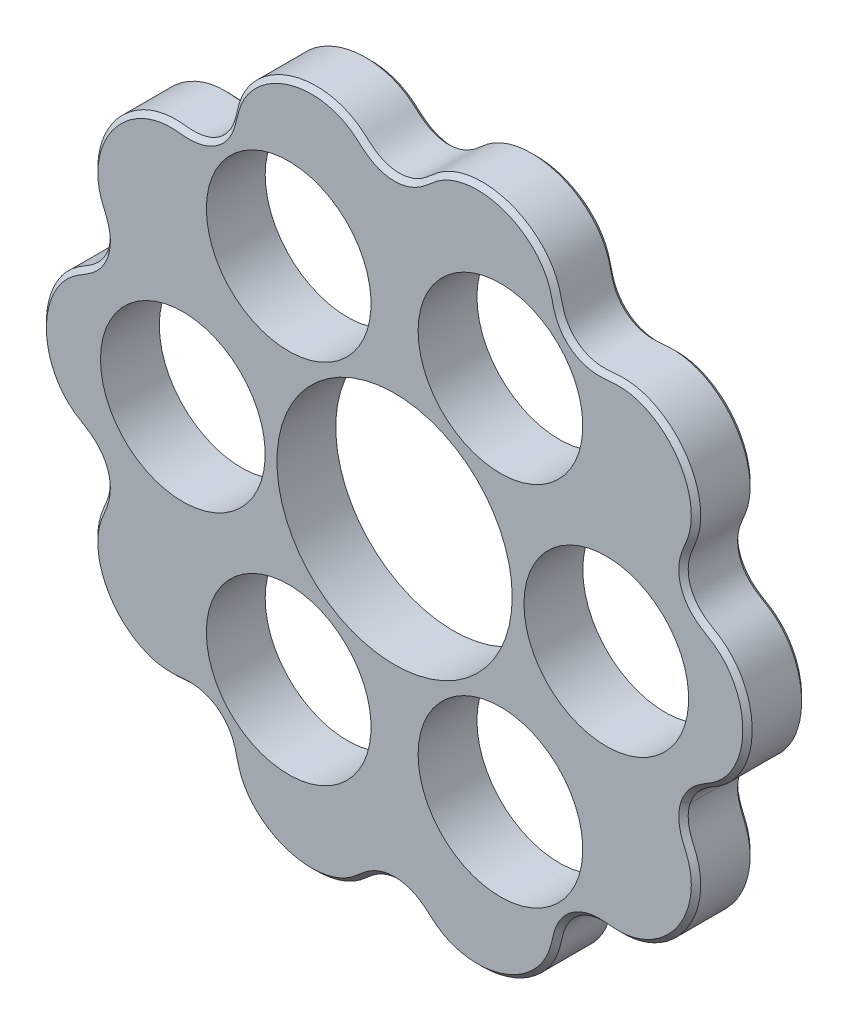
SolidWorks part; units mm, degrees
ref_plane "Front Plane" through (0, 0, 0) normal (0, 0, 1) x (1, 0, 0)
ref_plane "Top Plane" through (0, 0, 0) normal (0, 1, 0) x (1, 0, 0)
ref_plane "Right Plane" through (0, 0, 0) normal (1, 0, 0) x (0, 0, -1)
ref_plane "Plane1" through (0, 0, 2.5) normal (0, 0, -1) x (-1, 0, 0)
sketch "Sketch1" plane through (0, 0, 2.5) normal (0, 0, -1) x (-1, 0, 0)
  spline S0 degree 5 poles (13.3637, 4.0172) (13.3679, 4.0044) (13.3764, 3.979) (13.39, 3.941) (13.4096, 3.891) (13.4366, 3.8295) (13.466, 3.7691) (13.4977, 3.7099) (13.5318, 3.652) (13.5681, 3.5955) (13.6065, 3.5404) (13.647, 3.4868) (13.6895, 3.4348) (13.7339, 3.3844) (13.7801, 3.3357) (13.828, 3.2886) (13.8775, 3.2433) (13.9285, 3.1996) (13.9809, 3.1576) (14.0345, 3.1172) (14.0892, 3.0782) (14.1448, 3.0407) (14.2012, 3.0043) (14.2582, 2.9689) (14.3156, 2.934) (14.3731, 2.8995) (14.4306, 2.8649) (14.4879, 2.83) (14.5447, 2.7944) (14.601, 2.7578) (14.6567, 2.7203) (14.7115, 2.6816) (14.7655, 2.6417) (14.8185, 2.6005) (14.8705, 2.5581) (14.9216, 2.5145) (14.9715, 2.4697) (15.0204, 2.4237) (15.0682, 2.3765) (15.1148, 2.3283) (15.1604, 2.279) (15.2048, 2.2286) (15.248, 2.1773) (15.2901, 2.125) (15.3309, 2.0718) (15.3707, 2.0177) (15.4092, 1.9627) (15.4465, 1.9069) (15.4827, 1.8504) (15.5176, 1.7931) (15.5513, 1.735) (15.5839, 1.6763) (15.6152, 1.617) (15.6453, 1.557) (15.6742, 1.4964) (15.7019, 1.4353) (15.7283, 1.3736) (15.7536, 1.3114) (15.7776, 1.2487) (15.8004, 1.1856) (15.822, 1.1221) (15.8423, 1.0581) (15.8614, 0.9938) (15.8793, 0.9291) (15.896, 0.8641) (15.9114, 0.7988) (15.9256, 0.7332) (15.9386, 0.6673) (15.9503, 0.6012) (15.9608, 0.535) (15.97, 0.4685) (15.9781, 0.4019) (15.9849, 0.3351) (15.9904, 0.2682) (15.9947, 0.2012) (15.9978, 0.1342) (15.9997, 0.0671) (16.0003, 0) (15.9997, -0.0671) (15.9978, -0.1342) (15.9947, -0.2012) (15.9904, -0.2682) (15.9849, -0.3351) (15.9781, -0.4019) (15.97, -0.4685) (15.9608, -0.535) (15.9503, -0.6012) (15.9386, -0.6673) (15.9256, -0.7332) (15.9114, -0.7988) (15.896, -0.8641) (15.8793, -0.9291) (15.8614, -0.9938) (15.8423, -1.0581) (15.822, -1.1221) (15.8004, -1.1856) (15.7776, -1.2487) (15.7536, -1.3114) (15.7283, -1.3736) (15.7019, -1.4353) (15.6742, -1.4964) (15.6453, -1.557) (15.6152, -1.617) (15.5839, -1.6763) (15.5513, -1.735) (15.5176, -1.7931) (15.4827, -1.8504) (15.4465, -1.9069) (15.4092, -1.9627) (15.3707, -2.0177) (15.3309, -2.0718) (15.2901, -2.125) (15.248, -2.1773) (15.2048, -2.2286) (15.1604, -2.279) (15.1148, -2.3283) (15.0682, -2.3765) (15.0204, -2.4237) (14.9715, -2.4697) (14.9216, -2.5145) (14.8705, -2.5581) (14.8185, -2.6005) (14.7655, -2.6417) (14.7115, -2.6816) (14.6567, -2.7203) (14.601, -2.7578) (14.5447, -2.7944) (14.4879, -2.83) (14.4306, -2.8649) (14.3731, -2.8995) (14.3156, -2.934) (14.2582, -2.9689) (14.2012, -3.0043) (14.1448, -3.0407) (14.0892, -3.0782) (14.0345, -3.1172) (13.9809, -3.1576) (13.9285, -3.1996) (13.8775, -3.2433) (13.828, -3.2886) (13.7801, -3.3357) (13.7339, -3.3844) (13.6895, -3.4348) (13.647, -3.4868) (13.6065, -3.5404) (13.5681, -3.5955) (13.5318, -3.652) (13.4977, -3.7099) (13.466, -3.7691) (13.4366, -3.8295) (13.4096, -3.891) (13.3851, -3.9536) (13.3631, -4.017) (13.3436, -4.0813) (13.3267, -4.1463) (13.3124, -4.2119) (13.3006, -4.2781) (13.2915, -4.3446) (13.285, -4.4115) (13.2811, -4.4785) (13.2798, -4.5457) (13.2811, -4.6128) (13.2849, -4.6799) (13.2912, -4.7468) (13.3, -4.8133) (13.3111, -4.8796) (13.3245, -4.9454) (13.3401, -5.0107) (13.3578, -5.0754) (13.3774, -5.1397) (13.3987, -5.2033) (13.4217, -5.2664) (13.4459, -5.329) (13.4712, -5.3911) (13.4971, -5.453) (13.5234, -5.5147) (13.5496, -5.5765) (13.5753, -5.6385) (13.6004, -5.7007) (13.6245, -5.7633) (13.6474, -5.8264) (13.669, -5.89) (13.6892, -5.954) (13.7079, -6.0184) (13.7251, -6.0833) (13.7408, -6.1486) (13.7548, -6.2142) (13.7673, -6.2802) (13.7783, -6.3464) (13.7877, -6.4129) (13.7955, -6.4795) (13.8018, -6.5463) (13.8066, -6.6133) (13.8099, -6.6803) (13.8117, -6.7474) (13.8121, -6.8145) (13.8109, -6.8817) (13.8083, -6.9487) (13.8043, -7.0157) (13.7989, -7.0826) (13.7921, -7.1494) (13.7839, -7.216) (13.7744, -7.2824) (13.7635, -7.3487) (13.7513, -7.4147) (13.7377, -7.4804) (13.7229, -7.5458) (13.7067, -7.611) (13.6893, -7.6758) (13.6707, -7.7403) (13.6508, -7.8044) (13.6296, -7.8681) (13.6073, -7.9313) (13.5837, -7.9942) (13.559, -8.0566) (13.5331, -8.1185) (13.506, -8.1799) (13.4778, -8.2408) (13.4484, -8.3011) (13.418, -8.3609) (13.3864, -8.4202) (13.3537, -8.4788) (13.32, -8.5368) (13.2852, -8.5942) (13.2493, -8.6509) (13.2124, -8.7069) (13.1745, -8.7623) (13.1355, -8.817) (13.0956, -8.8709) (13.0546, -8.9241) (13.0127, -8.9765) (12.9699, -9.0281) (12.926, -9.079) (12.8813, -9.129) (12.8356, -9.1782) (12.7891, -9.2265) (12.7416, -9.274) (12.6933, -9.3205) (12.6441, -9.3662) (12.5941, -9.4109) (12.5432, -9.4547) (12.4915, -9.4975) (12.439, -9.5393) (12.3857, -9.5801) (12.3317, -9.6199) (12.2769, -9.6586) (12.2213, -9.6963) (12.1651, -9.7329) (12.1081, -9.7684) (12.0504, -9.8027) (11.9921, -9.8359) (11.9331, -9.8679) (11.8735, -9.8988) (11.8133, -9.9284) (11.7525, -9.9567) (11.6911, -9.9838) (11.6291, -10.0097) (11.5666, -10.0342) (11.5036, -10.0574) (11.4402, -10.0792) (11.3762, -10.0996) (11.3119, -10.1186) (11.2471, -10.1362) (11.1819, -10.1523) (11.1164, -10.167) (11.0506, -10.1801) (10.9845, -10.1917) (10.9181, -10.2018) (10.8515, -10.2103) (10.7848, -10.2172) (10.7179, -10.2225) (10.6508, -10.2262) (10.5838, -10.2283) (10.5166, -10.2289) (10.4495, -10.2279) (10.3825, -10.2256) (10.3154, -10.2221) (10.2485, -10.2175) (10.1816, -10.2121) (10.1148, -10.2063) (10.0479, -10.2004) (9.9811, -10.1948) (9.9141, -10.19) (9.8471, -10.1863) (9.7801, -10.184) (9.7129, -10.1833) (9.6458, -10.1845) (9.5787, -10.1877) (9.5118, -10.1931) (9.4451, -10.2007) (9.3787, -10.2106) (9.3126, -10.2228) (9.2471, -10.2375) (9.1821, -10.2546) (9.1179, -10.2741) (9.0544, -10.2961) (8.9918, -10.3205) (8.9303, -10.3474) (8.8698, -10.3766) (8.8105, -10.4082) (8.7525, -10.4421) (8.6959, -10.4783) (8.6408, -10.5167) (8.5873, -10.5572) (8.5354, -10.5999) (8.4852, -10.6445) (8.4368, -10.6912) (8.3903, -10.7396) (8.3458, -10.7899) (8.3032, -10.8419) (8.2627, -10.8954) (8.2243, -10.9505) (8.1879, -11.007) (8.1537, -11.0648) (8.1217, -11.1238) (8.0917, -11.1839) (8.0639, -11.245) (8.0381, -11.307) (8.0144, -11.3698) (7.9925, -11.4333) (7.9724, -11.4974) (7.9538, -11.5619) (7.9367, -11.6267) (7.9206, -11.6919) (7.9052, -11.7572) (7.8901, -11.8226) (7.875, -11.8879) (7.8595, -11.9532) (7.8431, -12.0183) (7.8258, -12.0831) (7.8073, -12.1476) (7.7874, -12.2118) (7.7661, -12.2754) (7.7434, -12.3386) (7.7192, -12.4012) (7.6934, -12.4632) (7.6663, -12.5245) (7.6376, -12.5852) (7.6075, -12.6452) (7.5761, -12.7045) (7.5432, -12.7631) (7.5091, -12.8208) (7.4736, -12.8778) (7.4369, -12.934) (7.3989, -12.9893) (7.3597, -13.0438) (7.3193, -13.0974) (7.2778, -13.1502) (7.2352, -13.202) (7.1915, -13.253) (7.1467, -13.303) (7.101, -13.3521) (7.0542, -13.4002) (7.0064, -13.4474) (6.9578, -13.4936) (6.9082, -13.5388) (6.8577, -13.583) (6.8063, -13.6262) (6.7542, -13.6685) (6.7012, -13.7096) (6.6474, -13.7498) (6.5928, -13.7889) (6.5376, -13.827) (6.4816, -13.864) (6.4249, -13.8999) (6.3675, -13.9347) (6.3095, -13.9685) (6.2509, -14.0012) (6.1917, -14.0328) (6.1319, -14.0632) (6.0716, -14.0926) (6.0107, -14.1208) (5.9493, -14.1479) (5.8874, -14.1739) (5.825, -14.1987) (5.7622, -14.2223) (5.699, -14.2448) (5.6354, -14.2661) (5.5713, -14.2863) (5.507, -14.3053) (5.4422, -14.323) (5.3772, -14.3396) (5.3119, -14.355) (5.2463, -14.3692) (5.1804, -14.3821) (5.1144, -14.3939) (5.0481, -14.4044) (4.9816, -14.4136) (4.915, -14.4216) (4.8482, -14.4284) (4.7813, -14.4339) (4.7143, -14.4382) (4.6473, -14.4411) (4.5802, -14.4428) (4.5131, -14.4433) (4.446, -14.4424) (4.3789, -14.4402) (4.3119, -14.4367) (4.2449, -14.432) (4.1781, -14.4258) (4.1114, -14.4184) (4.0449, -14.4097) (3.9785, -14.3996) (3.9124, -14.3881) (3.8465, -14.3753) (3.7809, -14.3611) (3.7156, -14.3456) (3.6506, -14.3287) (3.5861, -14.3105) (3.5219, -14.2908) (3.4581, -14.2697) (3.3949, -14.2473) (3.3321, -14.2235) (3.27, -14.1982) (3.2084, -14.1716) (3.1474, -14.1435) (3.0871, -14.114) (3.0275, -14.0831) (2.9686, -14.0509) (2.9105, -14.0172) (2.8533, -13.9822) (2.7969, -13.9458) (2.7414, -13.9081) (2.6867, -13.8691) (2.633, -13.8289) (2.5801, -13.7876) (2.528, -13.7453) (2.4765, -13.7022) (2.4256, -13.6586) (2.3749, -13.6146) (2.3243, -13.5705) (2.2735, -13.5267) (2.2221, -13.4835) (2.1701, -13.4411) (2.1172, -13.3998) (2.0633, -13.3598) (2.0083, -13.3213) (1.9521, -13.2845) (1.8948, -13.2495) (1.8364, -13.2164) (1.7769, -13.1854) (1.7162, -13.1565) (1.6546, -13.1298) (1.592, -13.1055) (1.5285, -13.0835) (1.4643, -13.064) (1.3993, -13.047) (1.3337, -13.0325) (1.2676, -13.0206) (1.2011, -13.0113) (1.1342, -13.0047) (1.0672, -13.0007) (1, -12.9993) (0.9328, -13.0007) (0.8658, -13.0047) (0.7989, -13.0113) (0.7324, -13.0206) (0.6663, -13.0325) (0.6007, -13.047) (0.5357, -13.064) (0.4715, -13.0835) (0.408, -13.1055) (0.3454, -13.1298) (0.2838, -13.1565) (0.2231, -13.1854) (0.1636, -13.2164) (0.1052, -13.2495) (0.0479, -13.2845) (-0.0083, -13.3213) (-0.0633, -13.3598) (-0.1172, -13.3998) (-0.1701, -13.4411) (-0.2221, -13.4835) (-0.2735, -13.5267) (-0.3243, -13.5705) (-0.3749, -13.6146) (-0.4256, -13.6586) (-0.4765, -13.7022) (-0.528, -13.7453) (-0.5801, -13.7876) (-0.633, -13.8289) (-0.6867, -13.8691) (-0.7414, -13.9081) (-0.7969, -13.9458) (-0.8533, -13.9822) (-0.9105, -14.0172) (-0.9686, -14.0509) (-1.0275, -14.0831) (-1.0871, -14.114) (-1.1474, -14.1435) (-1.2084, -14.1716) (-1.27, -14.1982) (-1.3321, -14.2235) (-1.3949, -14.2473) (-1.4581, -14.2697) (-1.5219, -14.2908) (-1.5861, -14.3105) (-1.6506, -14.3287) (-1.7156, -14.3456) (-1.7809, -14.3611) (-1.8465, -14.3753) (-1.9124, -14.3881) (-1.9785, -14.3996) (-2.0449, -14.4097) (-2.1114, -14.4184) (-2.1781, -14.4258) (-2.2449, -14.432) (-2.3119, -14.4367) (-2.3789, -14.4402) (-2.446, -14.4424) (-2.5131, -14.4433) (-2.5802, -14.4428) (-2.6473, -14.4411) (-2.7143, -14.4382) (-2.7813, -14.4339) (-2.8482, -14.4284) (-2.915, -14.4216) (-2.9816, -14.4136) (-3.0481, -14.4044) (-3.1144, -14.3939) (-3.1804, -14.3821) (-3.2463, -14.3692) (-3.3119, -14.355) (-3.3772, -14.3396) (-3.4422, -14.323) (-3.507, -14.3053) (-3.5713, -14.2863) (-3.6354, -14.2661) (-3.699, -14.2448) (-3.7622, -14.2223) (-3.825, -14.1987) (-3.8874, -14.1739) (-3.9493, -14.1479) (-4.0107, -14.1208) (-4.0716, -14.0926) (-4.1319, -14.0632) (-4.1917, -14.0328) (-4.2509, -14.0012) (-4.3095, -13.9685) (-4.3675, -13.9347) (-4.4249, -13.8999) (-4.4816, -13.864) (-4.5376, -13.827) (-4.5928, -13.7889) (-4.6474, -13.7498) (-4.7012, -13.7096) (-4.7542, -13.6685) (-4.8063, -13.6262) (-4.8577, -13.583) (-4.9082, -13.5388) (-4.9578, -13.4936) (-5.0064, -13.4474) (-5.0542, -13.4002) (-5.101, -13.3521) (-5.1467, -13.303) (-5.1915, -13.253) (-5.2352, -13.202) (-5.2778, -13.1502) (-5.3193, -13.0974) (-5.3597, -13.0438) (-5.3989, -12.9893) (-5.4369, -12.934) (-5.4736, -12.8778) (-5.5091, -12.8208) (-5.5432, -12.7631) (-5.5761, -12.7045) (-5.6075, -12.6452) (-5.6376, -12.5852) (-5.6663, -12.5245) (-5.6934, -12.4632) (-5.7192, -12.4012) (-5.7434, -12.3386) (-5.7661, -12.2754) (-5.7874, -12.2118) (-5.8073, -12.1476) (-5.8258, -12.0831) (-5.8431, -12.0183) (-5.8595, -11.9532) (-5.875, -11.8879) (-5.8901, -11.8226) (-5.9052, -11.7572) (-5.9206, -11.6919) (-5.9367, -11.6267) (-5.9538, -11.5619) (-5.9724, -11.4974) (-5.9925, -11.4333) (-6.0144, -11.3698) (-6.0381, -11.307) (-6.0639, -11.245) (-6.0917, -11.1839) (-6.1217, -11.1238) (-6.1537, -11.0648) (-6.1879, -11.007) (-6.2243, -10.9505) (-6.2627, -10.8954) (-6.3032, -10.8419) (-6.3458, -10.7899) (-6.3903, -10.7396) (-6.4368, -10.6912) (-6.4852, -10.6445) (-6.5354, -10.5999) (-6.5873, -10.5572) (-6.6408, -10.5167) (-6.6959, -10.4783) (-6.7525, -10.4421) (-6.8105, -10.4082) (-6.8698, -10.3766) (-6.9303, -10.3474) (-6.9918, -10.3205) (-7.0544, -10.2961) (-7.1179, -10.2741) (-7.1821, -10.2546) (-7.2471, -10.2375) (-7.3126, -10.2228) (-7.3787, -10.2106) (-7.4451, -10.2007) (-7.5118, -10.1931) (-7.5787, -10.1877) (-7.6458, -10.1845) (-7.7129, -10.1833) (-7.7801, -10.184) (-7.8471, -10.1863) (-7.9141, -10.19) (-7.9811, -10.1948) (-8.0479, -10.2004) (-8.1148, -10.2063) (-8.1816, -10.2121) (-8.2485, -10.2175) (-8.3154, -10.2221) (-8.3825, -10.2256) (-8.4495, -10.2279) (-8.5166, -10.2289) (-8.5838, -10.2283) (-8.6508, -10.2262) (-8.7179, -10.2225) (-8.7848, -10.2172) (-8.8515, -10.2103) (-8.9181, -10.2018) (-8.9845, -10.1917) (-9.0506, -10.1801) (-9.1164, -10.167) (-9.1819, -10.1523) (-9.2471, -10.1362) (-9.3119, -10.1186) (-9.3762, -10.0996) (-9.4402, -10.0792) (-9.5036, -10.0574) (-9.5666, -10.0342) (-9.6291, -10.0097) (-9.6911, -9.9838) (-9.7525, -9.9567) (-9.8133, -9.9284) (-9.8735, -9.8988) (-9.9331, -9.8679) (-9.9921, -9.8359) (-10.0504, -9.8027) (-10.1081, -9.7684) (-10.1651, -9.7329) (-10.2213, -9.6963) (-10.2769, -9.6586) (-10.3317, -9.6199) (-10.3857, -9.5801) (-10.439, -9.5393) (-10.4915, -9.4975) (-10.5432, -9.4547) (-10.5941, -9.4109) (-10.6441, -9.3662) (-10.6933, -9.3205) (-10.7416, -9.274) (-10.7891, -9.2265) (-10.8356, -9.1782) (-10.8813, -9.129) (-10.926, -9.079) (-10.9699, -9.0281) (-11.0127, -8.9765) (-11.0546, -8.9241) (-11.0956, -8.8709) (-11.1355, -8.817) (-11.1745, -8.7623) (-11.2124, -8.7069) (-11.2493, -8.6509) (-11.2852, -8.5942) (-11.32, -8.5368) (-11.3537, -8.4788) (-11.3864, -8.4202) (-11.418, -8.3609) (-11.4484, -8.3011) (-11.4778, -8.2408) (-11.506, -8.1799) (-11.5331, -8.1185) (-11.559, -8.0566) (-11.5837, -7.9942) (-11.6073, -7.9313) (-11.6296, -7.8681) (-11.6508, -7.8044) (-11.6707, -7.7403) (-11.6893, -7.6758) (-11.7067, -7.611) (-11.7229, -7.5458) (-11.7377, -7.4804) (-11.7513, -7.4147) (-11.7635, -7.3487) (-11.7744, -7.2824) (-11.7839, -7.216) (-11.7921, -7.1494) (-11.7989, -7.0826) (-11.8043, -7.0157) (-11.8083, -6.9487) (-11.8109, -6.8817) (-11.8121, -6.8145) (-11.8117, -6.7474) (-11.8099, -6.6803) (-11.8066, -6.6133) (-11.8018, -6.5463) (-11.7955, -6.4795) (-11.7877, -6.4129) (-11.7783, -6.3464) (-11.7673, -6.2802) (-11.7548, -6.2142) (-11.7408, -6.1486) (-11.7251, -6.0833) (-11.7079, -6.0184) (-11.6892, -5.954) (-11.669, -5.89) (-11.6474, -5.8264) (-11.6245, -5.7633) (-11.6004, -5.7007) (-11.5753, -5.6385) (-11.5496, -5.5765) (-11.5234, -5.5147) (-11.4971, -5.453) (-11.4712, -5.3911) (-11.4459, -5.329) (-11.4217, -5.2664) (-11.3987, -5.2033) (-11.3774, -5.1397) (-11.3578, -5.0754) (-11.3401, -5.0107) (-11.3245, -4.9454) (-11.3111, -4.8796) (-11.3, -4.8133) (-11.2912, -4.7468) (-11.2849, -4.6799) (-11.2811, -4.6128) (-11.2798, -4.5457) (-11.2811, -4.4785) (-11.285, -4.4115) (-11.2915, -4.3446) (-11.3006, -4.2781) (-11.3124, -4.2119) (-11.3267, -4.1463) (-11.3402, -4.0943) (-11.3515, -4.0556) (-11.3596, -4.03) (-11.3637, -4.0172) knots 50.343625 50.343625 50.343625 50.343625 50.343625 50.343625 50.41075 50.477875 50.545 50.612125 50.67925 50.746374 50.813499 50.880624 50.947749 51.014874 51.081999 51.149123 51.216248 51.283373 51.350498 51.417623 51.484748 51.551872 51.618997 51.686122 51.753247 51.820372 51.887497 51.954621 52.021746 52.088871 52.155996 52.223121 52.290246 52.35737 52.424495 52.49162 52.558745 52.62587 52.692995 52.760119 52.827244 52.894369 52.961494 53.028619 53.095744 53.162868 53.229993 53.297118 53.364243 53.431368 53.498493 53.565617 53.632742 53.699867 53.766992 53.834117 53.901242 53.968366 54.035491 54.102616 54.169741 54.236866 54.303991 54.371115 54.43824 54.505365 54.57249 54.639615 54.70674 54.773864 54.840989 54.908114 54.975239 55.042364 55.109489 55.176613 55.243738 55.310863 55.377988 55.445113 55.512238 55.579362 55.646487 55.713612 55.780737 55.847862 55.914987 55.982111 56.049236 56.116361 56.183486 56.250611 56.317736 56.38486 56.451985 56.51911 56.586235 56.65336 56.720485 56.787609 56.854734 56.921859 56.988984 57.056109 57.123234 57.190358 57.257483 57.324608 57.391733 57.458858 57.525983 57.593107 57.660232 57.727357 57.794482 57.861607 57.928732 57.995856 58.062981 58.130106 58.197231 58.264356 58.331481 58.398605 58.46573 58.532855 58.59998 58.667105 58.73423 58.801354 58.868479 58.935604 59.002729 59.069854 59.136979 59.204103 59.271228 59.338353 59.405478 59.472603 59.539728 59.606852 59.673977 59.741102 59.808227 59.875352 59.942477 60.009601 60.076726 60.143851 60.210976 60.278101 60.345226 60.41235 60.479475 60.5466 60.613725 60.68085 60.747975 60.815099 60.882224 60.949349 61.016474 61.083599 61.150724 61.217848 61.284973 61.352098 61.419223 61.486348 61.553473 61.620597 61.687722 61.754847 61.821972 61.889097 61.956222 62.023346 62.090471 62.157596 62.224721 62.291846 62.358971 62.426095 62.49322 62.560345 62.62747 62.694595 62.76172 62.828844 62.895969 62.963094 63.030219 63.097344 63.164469 63.231593 63.298718 63.365843 63.432968 63.500093 63.567218 63.634342 63.701467 63.768592 63.835717 63.902842 63.969967 64.037091 64.104216 64.171341 64.238466 64.305591 64.372716 64.43984 64.506965 64.57409 64.641215 64.70834 64.775465 64.842589 64.909714 64.976839 65.043964 65.111089 65.178214 65.245338 65.312463 65.379588 65.446713 65.513838 65.580963 65.648087 65.715212 65.782337 65.849462 65.916587 65.983712 66.050836 66.117961 66.185086 66.252211 66.319336 66.386461 66.453585 66.52071 66.587835 66.65496 66.722085 66.78921 66.856334 66.923459 66.990584 67.057709 67.124834 67.191959 67.259083 67.326208 67.393333 67.460458 67.527583 67.594708 67.661832 67.728957 67.796082 67.863207 67.930332 67.997457 68.064582 68.131706 68.198831 68.265956 68.333081 68.400206 68.467331 68.534455 68.60158 68.668705 68.73583 68.802955 68.87008 68.937204 69.004329 69.071454 69.138579 69.205704 69.272829 69.339953 69.407078 69.474203 69.541328 69.608453 69.675578 69.742702 69.809827 69.876952 69.944077 70.011202 70.078327 70.145451 70.212576 70.279701 70.346826 70.413951 70.481076 70.5482 70.615325 70.68245 70.749575 70.8167 70.883825 70.950949 71.018074 71.085199 71.152324 71.219449 71.286574 71.353698 71.420823 71.487948 71.555073 71.622198 71.689323 71.756447 71.823572 71.890697 71.957822 72.024947 72.092072 72.159196 72.226321 72.293446 72.360571 72.427696 72.494821 72.561945 72.62907 72.696195 72.76332 72.830445 72.89757 72.964694 73.031819 73.098944 73.166069 73.233194 73.300319 73.367443 73.434568 73.501693 73.568818 73.635943 73.703068 73.770192 73.837317 73.904442 73.971567 74.038692 74.105817 74.172941 74.240066 74.307191 74.374316 74.441441 74.508566 74.57569 74.642815 74.70994 74.777065 74.84419 74.911315 74.978439 75.045564 75.112689 75.179814 75.246939 75.314064 75.381188 75.448313 75.515438 75.582563 75.649688 75.716813 75.783937 75.851062 75.918187 75.985312 76.052437 76.119562 76.186686 76.253811 76.320936 76.388061 76.455186 76.522311 76.589435 76.65656 76.723685 76.79081 76.857935 76.92506 76.992184 77.059309 77.126434 77.193559 77.260684 77.327809 77.394933 77.462058 77.529183 77.596308 77.663433 77.730558 77.797682 77.864807 77.931932 77.999057 78.066182 78.133307 78.200431 78.267556 78.334681 78.401806 78.468931 78.536056 78.60318 78.670305 78.73743 78.804555 78.87168 78.938805 79.005929 79.073054 79.140179 79.207304 79.274429 79.341554 79.408678 79.475803 79.542928 79.610053 79.677178 79.744303 79.811427 79.878552 79.945677 80.012802 80.079927 80.147052 80.214176 80.281301 80.348426 80.415551 80.482676 80.549801 80.616925 80.68405 80.751175 80.8183 80.885425 80.95255 81.019674 81.086799 81.153924 81.221049 81.288174 81.355299 81.422423 81.489548 81.556673 81.623798 81.690923 81.758048 81.825172 81.892297 81.959422 82.026547 82.093672 82.160797 82.227921 82.295046 82.362171 82.429296 82.496421 82.563546 82.63067 82.697795 82.76492 82.832045 82.89917 82.966295 83.033419 83.100544 83.167669 83.234794 83.301919 83.369044 83.436168 83.503293 83.570418 83.637543 83.704668 83.771793 83.838917 83.906042 83.973167 84.040292 84.107417 84.174542 84.241666 84.308791 84.375916 84.443041 84.510166 84.577291 84.644415 84.71154 84.778665 84.84579 84.912915 84.98004 85.047164 85.114289 85.181414 85.248539 85.315664 85.382789 85.449913 85.517038 85.584163 85.651288 85.718413 85.785538 85.852662 85.919787 85.986912 86.054037 86.121162 86.188287 86.255411 86.322536 86.389661 86.456786 86.523911 86.591036 86.65816 86.725285 86.79241 86.859535 86.92666 86.993785 87.060909 87.128034 87.195159 87.262284 87.329409 87.396534 87.463658 87.530783 87.597908 87.665033 87.732158 87.799283 87.866407 87.933532 88.000657 88.067782 88.134907 88.202032 88.269156 88.336281 88.403406 88.470531 88.537656 88.604781 88.671905 88.73903 88.806155 88.87328 88.940405 89.00753 89.074654 89.141779 89.208904 89.276029 89.343154 89.410279 89.477403 89.544528 89.611653 89.678778 89.745903 89.813028 89.880152 89.947277 90.014402 90.081527 90.148652 90.215777 90.282901 90.350026 90.417151 90.484276 90.551401 90.618526 90.68565 90.752775 90.8199 90.887025 90.95415 91.021275 91.0884 91.155524 91.222649 91.289774 91.356899 91.424024 91.491149 91.558273 91.625398 91.692523 91.759648 91.826773 91.893898 91.961022 92.028147 92.095272 92.162397 92.229522 92.296647 92.363771 92.430896 92.498021 92.565146 92.632271 92.699396 92.76652 92.833645 92.90077 92.967895 93.03502 93.102145 93.169269 93.236394 93.303519 93.370644 93.437769 93.504894 93.572018 93.639143 93.706268 93.773393 93.840518 93.907643 93.974767 94.041892 94.109017 94.176142 94.243267 94.310392 94.377516 94.444641 94.511766 94.578891 94.646016 94.713141 94.780265 94.84739 94.914515 94.98164 95.048765 95.11589 95.183014 95.250139 95.317264 95.384389 95.451514 95.518639 95.585763 95.652888 95.720013 95.787138 95.854263 95.921388 95.988512 96.055637 96.122762 96.189887 96.257012 96.324137 96.391261 96.458386 96.525511 96.592636 96.659761 96.726886 96.79401 96.861135 96.92826 96.995385 97.06251 97.129635 97.196759 97.263884 97.331009 97.398134 97.465259 97.532384 97.599508 97.666633 97.733758 97.800883 97.868008 97.935133 98.002257 98.069382 98.136507 98.203632 98.270757 98.337882 98.405006 98.472131 98.539256 98.606381 98.673506 98.740631 98.807755 98.87488 98.942005 99.00913 99.076255 99.14338 99.210504 99.277629 99.344754 99.411879 99.479004 99.546129 99.613253 99.680378 99.747503 99.814628 99.881753 99.948878 100.016002 100.083127 100.150252 100.217377 100.284502 100.351627 100.418751 100.485876 100.553001 100.620126 100.687251 100.687251 100.687251 100.687251 100.687251 100.687251
  spline S1 degree 5 poles (-11.3637, -4.0172) (-11.3679, -4.0044) (-11.3764, -3.979) (-11.39, -3.941) (-11.4096, -3.891) (-11.4366, -3.8295) (-11.466, -3.7691) (-11.4977, -3.7099) (-11.5318, -3.652) (-11.5681, -3.5955) (-11.6065, -3.5404) (-11.647, -3.4868) (-11.6895, -3.4348) (-11.7339, -3.3844) (-11.7801, -3.3357) (-11.828, -3.2886) (-11.8775, -3.2433) (-11.9285, -3.1996) (-11.9809, -3.1576) (-12.0345, -3.1172) (-12.0892, -3.0782) (-12.1448, -3.0407) (-12.2012, -3.0043) (-12.2582, -2.9689) (-12.3156, -2.934) (-12.3731, -2.8995) (-12.4306, -2.8649) (-12.4879, -2.83) (-12.5447, -2.7944) (-12.601, -2.7578) (-12.6567, -2.7203) (-12.7115, -2.6816) (-12.7655, -2.6417) (-12.8185, -2.6005) (-12.8705, -2.5581) (-12.9216, -2.5145) (-12.9715, -2.4697) (-13.0204, -2.4237) (-13.0682, -2.3765) (-13.1148, -2.3283) (-13.1604, -2.279) (-13.2048, -2.2286) (-13.248, -2.1773) (-13.2901, -2.125) (-13.3309, -2.0718) (-13.3707, -2.0177) (-13.4092, -1.9627) (-13.4465, -1.9069) (-13.4827, -1.8504) (-13.5176, -1.7931) (-13.5513, -1.735) (-13.5839, -1.6763) (-13.6152, -1.617) (-13.6453, -1.557) (-13.6742, -1.4964) (-13.7019, -1.4353) (-13.7283, -1.3736) (-13.7536, -1.3114) (-13.7776, -1.2487) (-13.8004, -1.1856) (-13.822, -1.1221) (-13.8423, -1.0581) (-13.8614, -0.9938) (-13.8793, -0.9291) (-13.896, -0.8641) (-13.9114, -0.7988) (-13.9256, -0.7332) (-13.9386, -0.6673) (-13.9503, -0.6012) (-13.9608, -0.535) (-13.97, -0.4685) (-13.9781, -0.4019) (-13.9849, -0.3351) (-13.9904, -0.2682) (-13.9947, -0.2012) (-13.9978, -0.1342) (-13.9997, -0.0671) (-14.0003, 0) (-13.9997, 0.0671) (-13.9978, 0.1342) (-13.9947, 0.2012) (-13.9904, 0.2682) (-13.9849, 0.3351) (-13.9781, 0.4019) (-13.97, 0.4685) (-13.9608, 0.535) (-13.9503, 0.6012) (-13.9386, 0.6673) (-13.9256, 0.7332) (-13.9114, 0.7988) (-13.896, 0.8641) (-13.8793, 0.9291) (-13.8614, 0.9938) (-13.8423, 1.0581) (-13.822, 1.1221) (-13.8004, 1.1856) (-13.7776, 1.2487) (-13.7536, 1.3114) (-13.7283, 1.3736) (-13.7019, 1.4353) (-13.6742, 1.4964) (-13.6453, 1.557) (-13.6152, 1.617) (-13.5839, 1.6763) (-13.5513, 1.735) (-13.5176, 1.7931) (-13.4827, 1.8504) (-13.4465, 1.9069) (-13.4092, 1.9627) (-13.3707, 2.0177) (-13.3309, 2.0718) (-13.2901, 2.125) (-13.248, 2.1773) (-13.2048, 2.2286) (-13.1604, 2.279) (-13.1148, 2.3283) (-13.0682, 2.3765) (-13.0204, 2.4237) (-12.9715, 2.4697) (-12.9216, 2.5145) (-12.8705, 2.5581) (-12.8185, 2.6005) (-12.7655, 2.6417) (-12.7115, 2.6816) (-12.6567, 2.7203) (-12.601, 2.7578) (-12.5447, 2.7944) (-12.4879, 2.83) (-12.4306, 2.8649) (-12.3731, 2.8995) (-12.3156, 2.934) (-12.2582, 2.9689) (-12.2012, 3.0043) (-12.1448, 3.0407) (-12.0892, 3.0782) (-12.0345, 3.1172) (-11.9809, 3.1576) (-11.9285, 3.1996) (-11.8775, 3.2433) (-11.828, 3.2886) (-11.7801, 3.3357) (-11.7339, 3.3844) (-11.6895, 3.4348) (-11.647, 3.4868) (-11.6065, 3.5404) (-11.5681, 3.5955) (-11.5318, 3.652) (-11.4977, 3.7099) (-11.466, 3.7691) (-11.4366, 3.8295) (-11.4096, 3.891) (-11.3851, 3.9536) (-11.3631, 4.017) (-11.3436, 4.0813) (-11.3267, 4.1463) (-11.3124, 4.2119) (-11.3006, 4.2781) (-11.2915, 4.3446) (-11.285, 4.4115) (-11.2811, 4.4785) (-11.2798, 4.5457) (-11.2811, 4.6128) (-11.2849, 4.6799) (-11.2912, 4.7468) (-11.3, 4.8133) (-11.3111, 4.8796) (-11.3245, 4.9454) (-11.3401, 5.0107) (-11.3578, 5.0754) (-11.3774, 5.1397) (-11.3987, 5.2033) (-11.4217, 5.2664) (-11.4459, 5.329) (-11.4712, 5.3911) (-11.4971, 5.453) (-11.5234, 5.5147) (-11.5496, 5.5765) (-11.5753, 5.6385) (-11.6004, 5.7007) (-11.6245, 5.7633) (-11.6474, 5.8264) (-11.669, 5.89) (-11.6892, 5.954) (-11.7079, 6.0184) (-11.7251, 6.0833) (-11.7408, 6.1486) (-11.7548, 6.2142) (-11.7673, 6.2802) (-11.7783, 6.3464) (-11.7877, 6.4129) (-11.7955, 6.4795) (-11.8018, 6.5463) (-11.8066, 6.6133) (-11.8099, 6.6803) (-11.8117, 6.7474) (-11.8121, 6.8145) (-11.8109, 6.8817) (-11.8083, 6.9487) (-11.8043, 7.0157) (-11.7989, 7.0826) (-11.7921, 7.1494) (-11.7839, 7.216) (-11.7744, 7.2824) (-11.7635, 7.3487) (-11.7513, 7.4147) (-11.7377, 7.4804) (-11.7229, 7.5458) (-11.7067, 7.611) (-11.6893, 7.6758) (-11.6707, 7.7403) (-11.6508, 7.8044) (-11.6296, 7.8681) (-11.6073, 7.9313) (-11.5837, 7.9942) (-11.559, 8.0566) (-11.5331, 8.1185) (-11.506, 8.1799) (-11.4778, 8.2408) (-11.4484, 8.3011) (-11.418, 8.3609) (-11.3864, 8.4202) (-11.3537, 8.4788) (-11.32, 8.5368) (-11.2852, 8.5942) (-11.2493, 8.6509) (-11.2124, 8.7069) (-11.1745, 8.7623) (-11.1355, 8.817) (-11.0956, 8.8709) (-11.0546, 8.9241) (-11.0127, 8.9765) (-10.9699, 9.0281) (-10.926, 9.079) (-10.8813, 9.129) (-10.8356, 9.1782) (-10.7891, 9.2265) (-10.7416, 9.274) (-10.6933, 9.3205) (-10.6441, 9.3662) (-10.5941, 9.4109) (-10.5432, 9.4547) (-10.4915, 9.4975) (-10.439, 9.5393) (-10.3857, 9.5801) (-10.3317, 9.6199) (-10.2769, 9.6586) (-10.2213, 9.6963) (-10.1651, 9.7329) (-10.1081, 9.7684) (-10.0504, 9.8027) (-9.9921, 9.8359) (-9.9331, 9.8679) (-9.8735, 9.8988) (-9.8133, 9.9284) (-9.7525, 9.9567) (-9.6911, 9.9838) (-9.6291, 10.0097) (-9.5666, 10.0342) (-9.5036, 10.0574) (-9.4402, 10.0792) (-9.3762, 10.0996) (-9.3119, 10.1186) (-9.2471, 10.1362) (-9.1819, 10.1523) (-9.1164, 10.167) (-9.0506, 10.1801) (-8.9845, 10.1917) (-8.9181, 10.2018) (-8.8515, 10.2103) (-8.7848, 10.2172) (-8.7179, 10.2225) (-8.6508, 10.2262) (-8.5838, 10.2283) (-8.5166, 10.2289) (-8.4495, 10.2279) (-8.3825, 10.2256) (-8.3154, 10.2221) (-8.2485, 10.2175) (-8.1816, 10.2121) (-8.1148, 10.2063) (-8.0479, 10.2004) (-7.9811, 10.1948) (-7.9141, 10.19) (-7.8471, 10.1863) (-7.7801, 10.184) (-7.7129, 10.1833) (-7.6458, 10.1845) (-7.5787, 10.1877) (-7.5118, 10.1931) (-7.4451, 10.2007) (-7.3787, 10.2106) (-7.3126, 10.2228) (-7.2471, 10.2375) (-7.1821, 10.2546) (-7.1179, 10.2741) (-7.0544, 10.2961) (-6.9918, 10.3205) (-6.9303, 10.3474) (-6.8698, 10.3766) (-6.8105, 10.4082) (-6.7525, 10.4421) (-6.6959, 10.4783) (-6.6408, 10.5167) (-6.5873, 10.5572) (-6.5354, 10.5999) (-6.4852, 10.6445) (-6.4368, 10.6912) (-6.3903, 10.7396) (-6.3458, 10.7899) (-6.3032, 10.8419) (-6.2627, 10.8954) (-6.2243, 10.9505) (-6.1879, 11.007) (-6.1537, 11.0648) (-6.1217, 11.1238) (-6.0917, 11.1839) (-6.0639, 11.245) (-6.0381, 11.307) (-6.0144, 11.3698) (-5.9925, 11.4333) (-5.9724, 11.4974) (-5.9538, 11.5619) (-5.9367, 11.6267) (-5.9206, 11.6919) (-5.9052, 11.7572) (-5.8901, 11.8226) (-5.875, 11.8879) (-5.8595, 11.9532) (-5.8431, 12.0183) (-5.8258, 12.0831) (-5.8073, 12.1476) (-5.7874, 12.2118) (-5.7661, 12.2754) (-5.7434, 12.3386) (-5.7192, 12.4012) (-5.6934, 12.4632) (-5.6663, 12.5245) (-5.6376, 12.5852) (-5.6075, 12.6452) (-5.5761, 12.7045) (-5.5432, 12.7631) (-5.5091, 12.8208) (-5.4736, 12.8778) (-5.4369, 12.934) (-5.3989, 12.9893) (-5.3597, 13.0438) (-5.3193, 13.0974) (-5.2778, 13.1502) (-5.2352, 13.202) (-5.1915, 13.253) (-5.1467, 13.303) (-5.101, 13.3521) (-5.0542, 13.4002) (-5.0064, 13.4474) (-4.9578, 13.4936) (-4.9082, 13.5388) (-4.8577, 13.583) (-4.8063, 13.6262) (-4.7542, 13.6685) (-4.7012, 13.7096) (-4.6474, 13.7498) (-4.5928, 13.7889) (-4.5376, 13.827) (-4.4816, 13.864) (-4.4249, 13.8999) (-4.3675, 13.9347) (-4.3095, 13.9685) (-4.2509, 14.0012) (-4.1917, 14.0328) (-4.1319, 14.0632) (-4.0716, 14.0926) (-4.0107, 14.1208) (-3.9493, 14.1479) (-3.8874, 14.1739) (-3.825, 14.1987) (-3.7622, 14.2223) (-3.699, 14.2448) (-3.6354, 14.2661) (-3.5713, 14.2863) (-3.507, 14.3053) (-3.4422, 14.323) (-3.3772, 14.3396) (-3.3119, 14.355) (-3.2463, 14.3692) (-3.1804, 14.3821) (-3.1144, 14.3939) (-3.0481, 14.4044) (-2.9816, 14.4136) (-2.915, 14.4216) (-2.8482, 14.4284) (-2.7813, 14.4339) (-2.7143, 14.4382) (-2.6473, 14.4411) (-2.5802, 14.4428) (-2.5131, 14.4433) (-2.446, 14.4424) (-2.3789, 14.4402) (-2.3119, 14.4367) (-2.2449, 14.432) (-2.1781, 14.4258) (-2.1114, 14.4184) (-2.0449, 14.4097) (-1.9785, 14.3996) (-1.9124, 14.3881) (-1.8465, 14.3753) (-1.7809, 14.3611) (-1.7156, 14.3456) (-1.6506, 14.3287) (-1.5861, 14.3105) (-1.5219, 14.2908) (-1.4581, 14.2697) (-1.3949, 14.2473) (-1.3321, 14.2235) (-1.27, 14.1982) (-1.2084, 14.1716) (-1.1474, 14.1435) (-1.0871, 14.114) (-1.0275, 14.0831) (-0.9686, 14.0509) (-0.9105, 14.0172) (-0.8533, 13.9822) (-0.7969, 13.9458) (-0.7414, 13.9081) (-0.6867, 13.8691) (-0.633, 13.8289) (-0.5801, 13.7876) (-0.528, 13.7453) (-0.4765, 13.7022) (-0.4256, 13.6586) (-0.3749, 13.6146) (-0.3243, 13.5705) (-0.2735, 13.5267) (-0.2221, 13.4835) (-0.1701, 13.4411) (-0.1172, 13.3998) (-0.0633, 13.3598) (-0.0083, 13.3213) (0.0479, 13.2845) (0.1052, 13.2495) (0.1636, 13.2164) (0.2231, 13.1854) (0.2838, 13.1565) (0.3454, 13.1298) (0.408, 13.1055) (0.4715, 13.0835) (0.5357, 13.064) (0.6007, 13.047) (0.6663, 13.0325) (0.7324, 13.0206) (0.7989, 13.0113) (0.8658, 13.0047) (0.9328, 13.0007) (1, 12.9993) (1.0672, 13.0007) (1.1342, 13.0047) (1.2011, 13.0113) (1.2676, 13.0206) (1.3337, 13.0325) (1.3993, 13.047) (1.4643, 13.064) (1.5285, 13.0835) (1.592, 13.1055) (1.6546, 13.1298) (1.7162, 13.1565) (1.7769, 13.1854) (1.8364, 13.2164) (1.8948, 13.2495) (1.9521, 13.2845) (2.0083, 13.3213) (2.0633, 13.3598) (2.1172, 13.3998) (2.1701, 13.4411) (2.2221, 13.4835) (2.2735, 13.5267) (2.3243, 13.5705) (2.3749, 13.6146) (2.4256, 13.6586) (2.4765, 13.7022) (2.528, 13.7453) (2.5801, 13.7876) (2.633, 13.8289) (2.6867, 13.8691) (2.7414, 13.9081) (2.7969, 13.9458) (2.8533, 13.9822) (2.9105, 14.0172) (2.9686, 14.0509) (3.0275, 14.0831) (3.0871, 14.114) (3.1474, 14.1435) (3.2084, 14.1716) (3.27, 14.1982) (3.3321, 14.2235) (3.3949, 14.2473) (3.4581, 14.2697) (3.5219, 14.2908) (3.5861, 14.3105) (3.6506, 14.3287) (3.7156, 14.3456) (3.7809, 14.3611) (3.8465, 14.3753) (3.9124, 14.3881) (3.9785, 14.3996) (4.0449, 14.4097) (4.1114, 14.4184) (4.1781, 14.4258) (4.2449, 14.432) (4.3119, 14.4367) (4.3789, 14.4402) (4.446, 14.4424) (4.5131, 14.4433) (4.5802, 14.4428) (4.6473, 14.4411) (4.7143, 14.4382) (4.7813, 14.4339) (4.8482, 14.4284) (4.915, 14.4216) (4.9816, 14.4136) (5.0481, 14.4044) (5.1144, 14.3939) (5.1804, 14.3821) (5.2463, 14.3692) (5.3119, 14.355) (5.3772, 14.3396) (5.4422, 14.323) (5.507, 14.3053) (5.5713, 14.2863) (5.6354, 14.2661) (5.699, 14.2448) (5.7622, 14.2223) (5.825, 14.1987) (5.8874, 14.1739) (5.9493, 14.1479) (6.0107, 14.1208) (6.0716, 14.0926) (6.1319, 14.0632) (6.1917, 14.0328) (6.2509, 14.0012) (6.3095, 13.9685) (6.3675, 13.9347) (6.4249, 13.8999) (6.4816, 13.864) (6.5376, 13.827) (6.5928, 13.7889) (6.6474, 13.7498) (6.7012, 13.7096) (6.7542, 13.6685) (6.8063, 13.6262) (6.8577, 13.583) (6.9082, 13.5388) (6.9578, 13.4936) (7.0064, 13.4474) (7.0542, 13.4002) (7.101, 13.3521) (7.1467, 13.303) (7.1915, 13.253) (7.2352, 13.202) (7.2778, 13.1502) (7.3193, 13.0974) (7.3597, 13.0438) (7.3989, 12.9893) (7.4369, 12.934) (7.4736, 12.8778) (7.5091, 12.8208) (7.5432, 12.7631) (7.5761, 12.7045) (7.6075, 12.6452) (7.6376, 12.5852) (7.6663, 12.5245) (7.6934, 12.4632) (7.7192, 12.4012) (7.7434, 12.3386) (7.7661, 12.2754) (7.7874, 12.2118) (7.8073, 12.1476) (7.8258, 12.0831) (7.8431, 12.0183) (7.8595, 11.9532) (7.875, 11.8879) (7.8901, 11.8226) (7.9052, 11.7572) (7.9206, 11.6919) (7.9367, 11.6267) (7.9538, 11.5619) (7.9724, 11.4974) (7.9925, 11.4333) (8.0144, 11.3698) (8.0381, 11.307) (8.0639, 11.245) (8.0917, 11.1839) (8.1217, 11.1238) (8.1537, 11.0648) (8.1879, 11.007) (8.2243, 10.9505) (8.2627, 10.8954) (8.3032, 10.8419) (8.3458, 10.7899) (8.3903, 10.7396) (8.4368, 10.6912) (8.4852, 10.6445) (8.5354, 10.5999) (8.5873, 10.5572) (8.6408, 10.5167) (8.6959, 10.4783) (8.7525, 10.4421) (8.8105, 10.4082) (8.8698, 10.3766) (8.9303, 10.3474) (8.9918, 10.3205) (9.0544, 10.2961) (9.1179, 10.2741) (9.1821, 10.2546) (9.2471, 10.2375) (9.3126, 10.2228) (9.3787, 10.2106) (9.4451, 10.2007) (9.5118, 10.1931) (9.5787, 10.1877) (9.6458, 10.1845) (9.7129, 10.1833) (9.7801, 10.184) (9.8471, 10.1863) (9.9141, 10.19) (9.9811, 10.1948) (10.0479, 10.2004) (10.1148, 10.2063) (10.1816, 10.2121) (10.2485, 10.2175) (10.3154, 10.2221) (10.3825, 10.2256) (10.4495, 10.2279) (10.5166, 10.2289) (10.5838, 10.2283) (10.6508, 10.2262) (10.7179, 10.2225) (10.7848, 10.2172) (10.8515, 10.2103) (10.9181, 10.2018) (10.9845, 10.1917) (11.0506, 10.1801) (11.1164, 10.167) (11.1819, 10.1523) (11.2471, 10.1362) (11.3119, 10.1186) (11.3762, 10.0996) (11.4402, 10.0792) (11.5036, 10.0574) (11.5666, 10.0342) (11.6291, 10.0097) (11.6911, 9.9838) (11.7525, 9.9567) (11.8133, 9.9284) (11.8735, 9.8988) (11.9331, 9.8679) (11.9921, 9.8359) (12.0504, 9.8027) (12.1081, 9.7684) (12.1651, 9.7329) (12.2213, 9.6963) (12.2769, 9.6586) (12.3317, 9.6199) (12.3857, 9.5801) (12.439, 9.5393) (12.4915, 9.4975) (12.5432, 9.4547) (12.5941, 9.4109) (12.6441, 9.3662) (12.6933, 9.3205) (12.7416, 9.274) (12.7891, 9.2265) (12.8356, 9.1782) (12.8813, 9.129) (12.926, 9.079) (12.9699, 9.0281) (13.0127, 8.9765) (13.0546, 8.9241) (13.0956, 8.8709) (13.1355, 8.817) (13.1745, 8.7623) (13.2124, 8.7069) (13.2493, 8.6509) (13.2852, 8.5942) (13.32, 8.5368) (13.3537, 8.4788) (13.3864, 8.4202) (13.418, 8.3609) (13.4484, 8.3011) (13.4778, 8.2408) (13.506, 8.1799) (13.5331, 8.1185) (13.559, 8.0566) (13.5837, 7.9942) (13.6073, 7.9313) (13.6296, 7.8681) (13.6508, 7.8044) (13.6707, 7.7403) (13.6893, 7.6758) (13.7067, 7.611) (13.7229, 7.5458) (13.7377, 7.4804) (13.7513, 7.4147) (13.7635, 7.3487) (13.7744, 7.2824) (13.7839, 7.216) (13.7921, 7.1494) (13.7989, 7.0826) (13.8043, 7.0157) (13.8083, 6.9487) (13.8109, 6.8817) (13.8121, 6.8145) (13.8117, 6.7474) (13.8099, 6.6803) (13.8066, 6.6133) (13.8018, 6.5463) (13.7955, 6.4795) (13.7877, 6.4129) (13.7783, 6.3464) (13.7673, 6.2802) (13.7548, 6.2142) (13.7408, 6.1486) (13.7251, 6.0833) (13.7079, 6.0184) (13.6892, 5.954) (13.669, 5.89) (13.6474, 5.8264) (13.6245, 5.7633) (13.6004, 5.7007) (13.5753, 5.6385) (13.5496, 5.5765) (13.5234, 5.5147) (13.4971, 5.453) (13.4712, 5.3911) (13.4459, 5.329) (13.4217, 5.2664) (13.3987, 5.2033) (13.3774, 5.1397) (13.3578, 5.0754) (13.3401, 5.0107) (13.3245, 4.9454) (13.3111, 4.8796) (13.3, 4.8133) (13.2912, 4.7468) (13.2849, 4.6799) (13.2811, 4.6128) (13.2798, 4.5457) (13.2811, 4.4785) (13.285, 4.4115) (13.2915, 4.3446) (13.3006, 4.2781) (13.3124, 4.2119) (13.3267, 4.1463) (13.3402, 4.0943) (13.3515, 4.0556) (13.3596, 4.03) (13.3637, 4.0172) knots 0 0 0 0 0 0 0.067125 0.13425 0.201375 0.268499 0.335624 0.402749 0.469874 0.536999 0.604124 0.671248 0.738373 0.805498 0.872623 0.939748 1.006873 1.073997 1.141122 1.208247 1.275372 1.342497 1.409622 1.476746 1.543871 1.610996 1.678121 1.745246 1.812371 1.879495 1.94662 2.013745 2.08087 2.147995 2.21512 2.282244 2.349369 2.416494 2.483619 2.550744 2.617869 2.684993 2.752118 2.819243 2.886368 2.953493 3.020618 3.087742 3.154867 3.221992 3.289117 3.356242 3.423367 3.490491 3.557616 3.624741 3.691866 3.758991 3.826116 3.89324 3.960365 4.02749 4.094615 4.16174 4.228865 4.295989 4.363114 4.430239 4.497364 4.564489 4.631614 4.698738 4.765863 4.832988 4.900113 4.967238 5.034363 5.101487 5.168612 5.235737 5.302862 5.369987 5.437112 5.504236 5.571361 5.638486 5.705611 5.772736 5.839861 5.906985 5.97411 6.041235 6.10836 6.175485 6.24261 6.309734 6.376859 6.443984 6.511109 6.578234 6.645359 6.712483 6.779608 6.846733 6.913858 6.980983 7.048108 7.115232 7.182357 7.249482 7.316607 7.383732 7.450857 7.517981 7.585106 7.652231 7.719356 7.786481 7.853606 7.92073 7.987855 8.05498 8.122105 8.18923 8.256355 8.323479 8.390604 8.457729 8.524854 8.591979 8.659104 8.726228 8.793353 8.860478 8.927603 8.994728 9.061853 9.128977 9.196102 9.263227 9.330352 9.397477 9.464602 9.531726 9.598851 9.665976 9.733101 9.800226 9.867351 9.934475 10.0016 10.068725 10.13585 10.202975 10.2701 10.337224 10.404349 10.471474 10.538599 10.605724 10.672849 10.739973 10.807098 10.874223 10.941348 11.008473 11.075598 11.142722 11.209847 11.276972 11.344097 11.411222 11.478347 11.545471 11.612596 11.679721 11.746846 11.813971 11.881096 11.94822 12.015345 12.08247 12.149595 12.21672 12.283845 12.350969 12.418094 12.485219 12.552344 12.619469 12.686594 12.753718 12.820843 12.887968 12.955093 13.022218 13.089343 13.156467 13.223592 13.290717 13.357842 13.424967 13.492092 13.559216 13.626341 13.693466 13.760591 13.827716 13.894841 13.961965 14.02909 14.096215 14.16334 14.230465 14.29759 14.364714 14.431839 14.498964 14.566089 14.633214 14.700339 14.767463 14.834588 14.901713 14.968838 15.035963 15.103088 15.170212 15.237337 15.304462 15.371587 15.438712 15.505837 15.572961 15.640086 15.707211 15.774336 15.841461 15.908586 15.97571 16.042835 16.10996 16.177085 16.24421 16.311335 16.378459 16.445584 16.512709 16.579834 16.646959 16.714084 16.781208 16.848333 16.915458 16.982583 17.049708 17.116833 17.183957 17.251082 17.318207 17.385332 17.452457 17.519582 17.586706 17.653831 17.720956 17.788081 17.855206 17.922331 17.989455 18.05658 18.123705 18.19083 18.257955 18.32508 18.392204 18.459329 18.526454 18.593579 18.660704 18.727829 18.794953 18.862078 18.929203 18.996328 19.063453 19.130578 19.197702 19.264827 19.331952 19.399077 19.466202 19.533327 19.600451 19.667576 19.734701 19.801826 19.868951 19.936076 20.0032 20.070325 20.13745 20.204575 20.2717 20.338825 20.405949 20.473074 20.540199 20.607324 20.674449 20.741574 20.808698 20.875823 20.942948 21.010073 21.077198 21.144323 21.211447 21.278572 21.345697 21.412822 21.479947 21.547072 21.614196 21.681321 21.748446 21.815571 21.882696 21.949821 22.016945 22.08407 22.151195 22.21832 22.285445 22.35257 22.419694 22.486819 22.553944 22.621069 22.688194 22.755319 22.822444 22.889568 22.956693 23.023818 23.090943 23.158068 23.225193 23.292317 23.359442 23.426567 23.493692 23.560817 23.627942 23.695066 23.762191 23.829316 23.896441 23.963566 24.030691 24.097815 24.16494 24.232065 24.29919 24.366315 24.43344 24.500564 24.567689 24.634814 24.701939 24.769064 24.836189 24.903313 24.970438 25.037563 25.104688 25.171813 25.238938 25.306062 25.373187 25.440312 25.507437 25.574562 25.641687 25.708811 25.775936 25.843061 25.910186 25.977311 26.044436 26.11156 26.178685 26.24581 26.312935 26.38006 26.447185 26.514309 26.581434 26.648559 26.715684 26.782809 26.849934 26.917058 26.984183 27.051308 27.118433 27.185558 27.252683 27.319807 27.386932 27.454057 27.521182 27.588307 27.655432 27.722556 27.789681 27.856806 27.923931 27.991056 28.058181 28.125305 28.19243 28.259555 28.32668 28.393805 28.46093 28.528054 28.595179 28.662304 28.729429 28.796554 28.863679 28.930803 28.997928 29.065053 29.132178 29.199303 29.266428 29.333552 29.400677 29.467802 29.534927 29.602052 29.669177 29.736301 29.803426 29.870551 29.937676 30.004801 30.071926 30.13905 30.206175 30.2733 30.340425 30.40755 30.474675 30.541799 30.608924 30.676049 30.743174 30.810299 30.877424 30.944548 31.011673 31.078798 31.145923 31.213048 31.280173 31.347297 31.414422 31.481547 31.548672 31.615797 31.682922 31.750046 31.817171 31.884296 31.951421 32.018546 32.085671 32.152795 32.21992 32.287045 32.35417 32.421295 32.48842 32.555544 32.622669 32.689794 32.756919 32.824044 32.891169 32.958293 33.025418 33.092543 33.159668 33.226793 33.293918 33.361042 33.428167 33.495292 33.562417 33.629542 33.696667 33.763791 33.830916 33.898041 33.965166 34.032291 34.099416 34.16654 34.233665 34.30079 34.367915 34.43504 34.502165 34.569289 34.636414 34.703539 34.770664 34.837789 34.904914 34.972038 35.039163 35.106288 35.173413 35.240538 35.307663 35.374787 35.441912 35.509037 35.576162 35.643287 35.710412 35.777536 35.844661 35.911786 35.978911 36.046036 36.113161 36.180285 36.24741 36.314535 36.38166 36.448785 36.51591 36.583034 36.650159 36.717284 36.784409 36.851534 36.918659 36.985783 37.052908 37.120033 37.187158 37.254283 37.321408 37.388532 37.455657 37.522782 37.589907 37.657032 37.724157 37.791281 37.858406 37.925531 37.992656 38.059781 38.126906 38.19403 38.261155 38.32828 38.395405 38.46253 38.529655 38.596779 38.663904 38.731029 38.798154 38.865279 38.932404 38.999528 39.066653 39.133778 39.200903 39.268028 39.335153 39.402277 39.469402 39.536527 39.603652 39.670777 39.737902 39.805026 39.872151 39.939276 40.006401 40.073526 40.140651 40.207775 40.2749 40.342025 40.40915 40.476275 40.5434 40.610524 40.677649 40.744774 40.811899 40.879024 40.946149 41.013273 41.080398 41.147523 41.214648 41.281773 41.348898 41.416022 41.483147 41.550272 41.617397 41.684522 41.751647 41.818771 41.885896 41.953021 42.020146 42.087271 42.154396 42.22152 42.288645 42.35577 42.422895 42.49002 42.557145 42.624269 42.691394 42.758519 42.825644 42.892769 42.959894 43.027018 43.094143 43.161268 43.228393 43.295518 43.362643 43.429767 43.496892 43.564017 43.631142 43.698267 43.765392 43.832516 43.899641 43.966766 44.033891 44.101016 44.168141 44.235265 44.30239 44.369515 44.43664 44.503765 44.57089 44.638014 44.705139 44.772264 44.839389 44.906514 44.973639 45.040763 45.107888 45.175013 45.242138 45.309263 45.376388 45.443513 45.510637 45.577762 45.644887 45.712012 45.779137 45.846262 45.913386 45.980511 46.047636 46.114761 46.181886 46.249011 46.316135 46.38326 46.450385 46.51751 46.584635 46.65176 46.718884 46.786009 46.853134 46.920259 46.987384 47.054509 47.121633 47.188758 47.255883 47.323008 47.390133 47.457258 47.524382 47.591507 47.658632 47.725757 47.792882 47.860007 47.927131 47.994256 48.061381 48.128506 48.195631 48.262756 48.32988 48.397005 48.46413 48.531255 48.59838 48.665505 48.732629 48.799754 48.866879 48.934004 49.001129 49.068254 49.135378 49.202503 49.269628 49.336753 49.403878 49.471003 49.538127 49.605252 49.672377 49.739502 49.806627 49.873752 49.940876 50.008001 50.075126 50.142251 50.209376 50.276501 50.343625 50.343625 50.343625 50.343625 50.343625 50.343625
extrude "Boss-Extrude1" add sketch "Sketch1" against normal blind 2.5
hole_wizard "Ø10.0 (10) Diameter Hole1" positions "Sketch3" profile "Sketch2" hole size "Ø10.0" standard "ANSI Metric"
sketch "Sketch3" plane through (0, 0, 5) normal (0, 0, 1) x (1, 0, 0)
  point P0 (-1, 0)
sketch "Sketch2" plane through (-1, 0, 5) normal (1, 0, 0) x (0, -1, 0)
  line L0 (0, 0) -> (0, 2.5)
  line L1 (0, 2.5) -> (5, 2.5)
  line L2 (5, 2.5) -> (5, 0)
  line L5 (5, 0) -> (0, 0)
  line L11 (0, -6.35) -> (0, 107.95) construction
  dimension "Thru Hole Dia." = 10
  dimension "Thru Hole Depth" = 2.5
hole_wizard "Ø7.0 (7) Diameter Hole1" positions "Sketch5" profile "Sketch4" hole size "Ø7.0" standard "ANSI Metric"
sketch "Sketch5" plane through (0, 0, 2.5) normal (0, 0, -1) x (-1, 0, 0)
  point P0 (5.5, 7.7942)
  point P1 (5.5, -7.7942)
  point P2 (-3.5, -7.7942)
  point P3 (-3.5, 7.7942)
  point P4 (10, 0)
  point P5 (-8, 0)
sketch "Sketch4" plane through (-5.5, 7.7942, 2.5) normal (1, 0, 0) x (0, 1, 0)
  line L0 (0, 0) -> (0, 2.5)
  line L1 (0, 2.5) -> (3.5, 2.5)
  line L2 (3.5, 2.5) -> (3.5, 0)
  line L5 (3.5, 0) -> (0, 0)
  line L11 (0, -6.35) -> (0, 107.95) construction
  dimension "Thru Hole Dia." = 7
  dimension "Thru Hole Depth" = 2.5
chamfer "Chamfer1" distance 0.2 angle 45 4 edges
